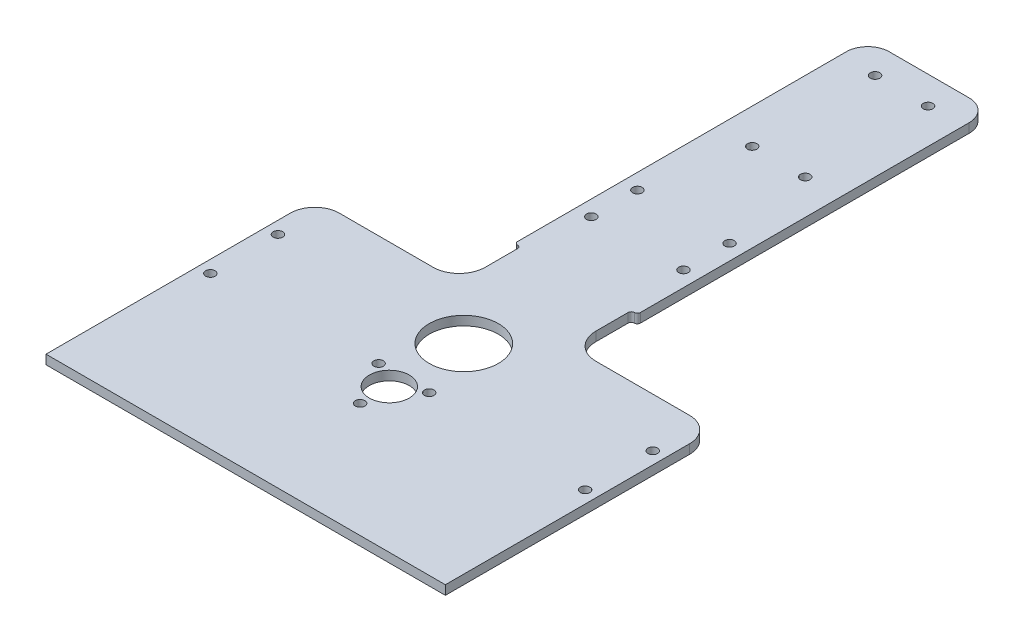
SolidWorks part; units mm, degrees
ref_plane "前视基准面" through (0, 0, 0) normal (0, 0, 1) x (1, 0, 0)
ref_plane "上视基准面" through (0, 0, 0) normal (0, 1, 0) x (1, 0, 0)
ref_plane "右视基准面" through (0, 0, 0) normal (1, 0, 0) x (0, 0, -1)
sketch "草图1" plane through (0, 0, 0) normal (0, 1, 0) x (1, 0, 0)
  line L1 (-100, 100) -> (100, 100)
  line L2 (-100, 100) -> (-100, -100)
  line L3 (-100, -100) -> (100, -100)
  line L4 (100, 100) -> (100, -100)
  line L5 (-100, 100) -> (100, -100) construction
  line L6 (-100, -100) -> (100, 100) construction
  point P0 (0, 0)
  dimension "D1" = 200
  dimension "D2" = 200
extrude "凸台-拉伸1" add sketch "草图1" along normal blind 3
sketch "草图2" plane through (0, 3, 0) normal (0, 1, 0) x (1, 0, 0)
  line L0 (0, 0) -> (0, 91) construction
  line L1 (-100, -100) -> (100, -100) construction
  line L2 (100, 100) -> (-100, 100) construction
  line L3 (-100, 0) -> (100, 0) construction
  line L5 (-100, 100) -> (-100, -100) construction
  line L6 (100, -100) -> (100, 100) construction
  line L7 (-29.5, 0) -> (29.5, 0) construction
  line L8 (-10, 100) -> (10, 100) construction
  line L9 (-10, 100) -> (-10, -100) construction
  line L10 (10, 100) -> (10, -100) construction
  line L11 (0, 0) -> (0, -29) construction
  line L13 (0, -29) -> (0, -32) construction
  circle A0 centre (-29.5, 0) radius 22.5 construction
  circle A1 centre (29.5, 0) radius 22.5 construction
  circle A2 centre (0, -29) radius 10.05 construction
  circle A3 centre (29.5, 0) radius 9.5 construction
  circle A4 centre (29.5, 0) radius 8 construction
  circle A5 centre (-29.5, 0) radius 8 construction
  circle A6 centre (-29.5, 0) radius 9.5 construction
  circle A7 centre (29.5, 9.5) radius 1.5
  circle A8 centre (21.5, 0) radius 1.5
  circle A9 centre (29.5, -9.5) radius 1.5
  circle A10 centre (37.5, 0) radius 1.5
  circle A11 centre (-29.5, -9.5) radius 1.5
  circle A12 centre (-37.5, 0) radius 1.5
  circle A13 centre (-21.5, 0) radius 1.5
  circle A14 centre (-29.5, 9.5) radius 1.5
  point P16 (0, 0)
  dimension "D1" = 45
  dimension "D3" = 20.1
  dimension "D4" = 19
  dimension "D5" = 16
  dimension "D6" = 3
  dimension "D7" = 3
  dimension "D2" = 20
  dimension "D9" = 3
  dimension "D10" = 29
extrude "切除-拉伸2" cut sketch "草图2" against normal blind 10
sketch "草图4" plane through (0, 3, 0) normal (0, 1, 0) x (1, 0, 0)
  line L0 (0, 0) -> (0, 91) construction
  line L1 (100, 100) -> (-100, 100) construction
  line L2 (-10, 100) -> (10, 100)
  line L3 (-10, 100) -> (-10, -100) construction
  line L4 (-100, -100) -> (100, -100) construction
  line L5 (10, 100) -> (10, -100) construction
  line L6 (21.5, 0) -> (37.5, 0)
  line L7 (-29.5, 0) -> (0, 0) construction
  line L8 (0, -29) -> (0, 0) construction
  circle A0 centre (0, -29) radius 11.25
  circle A1 centre (29.5, 0) radius 8 construction
  circle A2 centre (29.5, 0) radius 9.5 construction
  circle A3 centre (29.5, 0) radius 22.5 construction
  circle A4 centre (-29.5, 0) radius 9.5 construction
  circle A5 centre (-29.5, 0) radius 8 construction
  circle A6 centre (-29.5, 0) radius 22.5 construction
  dimension "D1" = 22.5
  dimension "D2" = 19
  dimension "D3" = 16
  dimension "D4" = 45
sketch "草图5" plane through (0, 3, 0) normal (0, 1, 0) x (1, 0, 0)
  line L0 (-44.5, -100) -> (-100, -100)
  line L2 (44.5, 0) -> (44.5, -100)
  line L4 (-20, 47.5) -> (-20, 24.995)
  line L6 (-44.5, 0) -> (-44.5, -100)
  line L7 (-100, -100) -> (100, -100) construction
  line L8 (20, 47.5) -> (20, 24.995)
  line L9 (-100, -100) -> (-100, 100)
  line L10 (0, 0) -> (0, 91) construction
  line L11 (0, 47.5) -> (-20, 47.5)
  line L12 (44.5, -100) -> (-44.5, -100)
  line L13 (0, 47.5) -> (20, 47.5)
  line L14 (-100, 100) -> (100, 100)
  line L15 (100, 100) -> (100, -100)
  line L16 (100, -100) -> (44.5, -100)
  arc A0 (29.8, 14.997) -> (44.5, 0) centre (29.5, 0) cw
  arc A1 (20, 24.995) -> (29.8, 14.997) centre (30, 24.995) ccw
  arc A2 (-29.8, 14.997) -> (-44.5, 0) centre (-29.5, 0) ccw
  arc A3 (-20, 24.995) -> (-29.8, 14.997) centre (-30, 24.995) cw
  line M11 (100, -100) -> (100, 100)
  line M12 (100, 100) -> (-100, 100)
  line M13 (-100, 100) -> (-100, -100)
  line M14 (-100, -100) -> (100, -100)
  dimension "D1" = 10
  dimension "D2" = 15
extrude "切除-拉伸3" cut sketch "草图5" against normal blind 10 contours A3 L4 L11 L13 L8 A1 A0 L2 L6 A2 M14 M11 M12 M13 region at (-72.25, 3, 97.1716)
sketch "草图6" plane through (0, 0, 0) normal (0, -1, 0) x (1, 0, 0)
  line L0 (20, -47.5) -> (-20, -47.5) construction
  line L7 (-20, -47.5) -> (-20, -24.995) construction
  circle A1 centre (-15, -42.5) radius 1.55
  circle A2 centre (-15, -27.5) radius 1.55
  circle A3 centre (15, -27.5) radius 1.55
  circle A4 centre (15, -42.5) radius 1.55
  dimension "D1" = 3.1
  dimension "D2" = 5
  dimension "D3" = 5
  dimension "D4" = 30
extrude "φ3.1通孔1" cut sketch "草图6" against normal blind 10
sketch "草图9" plane through (0, 3, 0) normal (0, 1, 0) x (1, 0, 0)
  line L0 (-20, 47.5) -> (-20, 26.3383)
  line L4 (-20, 47.5) -> (20, 47.5)
  line L5 (20, 47.5) -> (20, 26.3383)
  line L8 (12.2609, 20.995) -> (-12.2609, 20.995)
  arc A0 (-18.8003, 24.5054) -> (-13.4605, 21.3948) centre (-29.5, 0) cw
  arc A1 (18.8003, 24.5054) -> (13.4605, 21.3948) centre (29.5, 0) ccw
  arc A2 (18.8003, 24.5054) -> (20, 26.3383) centre (18, 26.3383) ccw
  arc A3 (13.4605, 21.3948) -> (12.2609, 20.995) centre (12.2609, 22.995) cw
  arc A4 (-12.2609, 20.995) -> (-13.4605, 21.3948) centre (-12.2609, 22.995) cw
  arc A5 (-18.8003, 24.5054) -> (-20, 26.3383) centre (-18, 26.3383) cw
  point P20 (-20, 24.995)
  dimension "D1" = 2
sketch "草图11" plane through (0, 3, 0) normal (0, 1, 0) x (1, 0, 0)
  line L0 (44.5, -17.5) -> (44.5, -100)
  line L1 (20, 47.5) -> (20, 7.5)
  line L2 (-44.5, 0) -> (-44.5, -100) construction
  line L3 (-44.5, -17.5) -> (-44.5, -100)
  line L4 (0, 47.5) -> (0, -100) construction
  line L5 (20, 47.5) -> (-20, 47.5) construction
  line L6 (-44.5, -100) -> (44.5, -100) construction
  line L7 (18, -4) -> (18, 6.5)
  line L8 (20, 7.5) -> (19, 7.5)
  line L9 (-39.5, -12.5) -> (-44.5, -12.5)
  line L10 (26.5, -12.5) -> (39.5, -12.5)
  line L11 (20, 47.5) -> (101.1331, 47.5)
  line L12 (101.1331, 47.5) -> (101.1331, -100)
  line L13 (101.1331, -100) -> (44.5, -100)
  line L14 (-20, 47.5) -> (-20, 7.5)
  line L15 (-20, 7.5) -> (-19, 7.5)
  line L16 (-18, -4) -> (-18, 6.5)
  line L17 (-26.5, -12.5) -> (-39.5, -12.5)
  line L18 (-44.5, -12.5) -> (-44.5, -17.5)
  line L19 (-101.1331, -100) -> (-44.5, -100)
  line L20 (-101.1331, 47.5) -> (-101.1331, -100)
  line L21 (-20, 47.5) -> (-101.1331, 47.5)
  line L22 (39.5, -12.5) -> (44.5, -12.5)
  line L23 (44.5, 0) -> (44.5, -100) construction
  line L24 (44.5, -12.5) -> (44.5, -17.5)
  arc A0 (26.5, -12.5) -> (18, -4) centre (26.5, -4) cw
  circle A2 centre (29.5, -9.5) radius 1.5
  circle A4 centre (21.5, 0) radius 1.5
  arc A5 (18, 6.5) -> (19, 7.5) centre (19, 6.5) cw
  arc A6 (-18, 6.5) -> (-19, 7.5) centre (-19, 6.5) ccw
  arc A7 (-26.5, -12.5) -> (-18, -4) centre (-26.5, -4) ccw
  point P21 (-44.5, -12.5)
  dimension "D1" = 8.5
  dimension "D2" = 1
extrude "切除-拉伸6" cut sketch "草图11" against normal up to next
extrude "φ22.5落弹孔" cut sketch "草图4" against normal up to next contours A0 region at (0, 3, 29)
fillet "圆角1" radius 1 2 edges at (-20, 1.5, -7.5) (20, 1.5, -7.5)
sketch "草图12" plane through (0, 0, -47.5) normal (0, 0, -1) x (-1, 0, 0)
  line L0 (-20, 3) -> (-20, 0)
  line L1 (-20, 0) -> (20, 0)
  line L2 (20, 0) -> (20, 3)
  line L3 (20, 3) -> (-20, 3)
extrude "凸台-拉伸2" add sketch "草图12" along normal blind 75
fillet "圆角2" radius 7 2 edges at (-20, 1.5, -122.5) (20, 1.5, -122.5)
sketch "草图13" plane through (0, 3, 0) normal (0, 1, 0) x (1, 0, 0)
  line L0 (-20, 115.5) -> (-20, 8.5) construction
  line L1 (0, 122.5) -> (0, 107.278)
  line L2 (-13, 122.5) -> (13, 122.5) construction
  circle A0 centre (-8.625, 73.5) radius 1.55
  circle A1 centre (-15, 42.5) radius 1.55
  circle A2 centre (-8.625, 113.5) radius 1.55
  circle A3 centre (8.625, 73.5) radius 1.55
  circle A4 centre (8.625, 113.5) radius 1.55
  dimension "D3" = 3.1
  dimension "D5" = 3.1
  dimension "D1" = 31
  dimension "D2" = 11.375
  dimension "D4" = 40
extrude "φ3.1通孔" cut sketch "草图13" against normal blind 10 contours A2 | A4 | A3 | A0 region at (-8.625, 3, -73.5) region at (-8.625, 3, -113.5) region at (8.625, 3, -73.5) region at (8.625, 3, -113.5)
sketch "草图16" plane through (0, 3, 0) normal (0, 1, 0) x (1, 0, 0)
  circle A0 centre (0, -53.25) radius 13 construction
  circle A2 centre (0, -53.25) radius 33 construction
  circle A3 centre (0, -53.25) radius 35.5 construction
  circle A4 centre (0, -53.25) radius 9.5 construction
  circle A5 centre (0, -62.75) radius 1.55
  circle A6 centre (-8.2272, -48.5) radius 1.55
  circle A7 centre (8.2272, -48.5) radius 1.55
  circle A8 centre (0, -53.25) radius 6.5
  point P16 (0, -53.25)
  dimension "D1" = 26
  dimension "D2" = 66
  dimension "D3" = 71
  dimension "D4" = 19
  dimension "D5" = 3.1
  dimension "D7" = 13
  dimension "D6" = 3
extrude "拨弹电机固定" cut sketch "草图16" against normal blind 10
sketch "草图18" plane through (-44.5, 0, 0) normal (-1, 0, 0) x (0, 0, 1)
  line L0 (12.5, 3) -> (12.5, 0)
  line L1 (12.5, 0) -> (100, 0)
  line L2 (100, 0) -> (100, 3)
  line L3 (100, 3) -> (12.5, 3)
extrude "凸台-拉伸3" add sketch "草图18" along normal blind 20.5
sketch "草图19" plane through (44.5, 0, 0) normal (1, 0, 0) x (0, 0, -1)
  line L0 (-100, 3) -> (-100, 0)
  line L1 (-100, 0) -> (-12.5, 0)
  line L2 (-12.5, 0) -> (-12.5, 3)
  line L3 (-12.5, 3) -> (-100, 3)
extrude "凸台-拉伸4" add sketch "草图19" along normal blind 20.5
sketch "草图7" plane through (0, 3, 0) normal (0, 1, 0) x (1, 0, 0)
  line L0 (0, -29) -> (0, -14.1048)
  line L1 (-25.4783, -39.524) -> (-25.4783, -40.524)
  line L3 (-65, -100) -> (-65, -12.5) construction
  circle A0 centre (-61, -50.5) radius 1.55
  circle A1 centre (-61, -28.5) radius 1.55
  circle A3 centre (61, -50.5) radius 1.55
  circle A4 centre (61, -28.5) radius 1.55
  point P9 (-51, -22.5)
  dimension "D1" = 4
  dimension "D3" = 3.1
  dimension "D4" = 22
  dimension "D2" = 10
extrude "切除-拉伸7" cut sketch "草图7" against normal blind 20.5 contours A1 | A0 | A4 | A3 region at (-61, 3, 50.5) region at (-61, 3, 28.5) region at (61, 3, 50.5) region at (61, 3, 28.5)
fillet "圆角3" radius 8 2 edges at (65, 1.5, 12.5) (-65, 1.5, 12.5)
sketch "草图20" plane through (0, 3, 0) normal (0, 1, 0) x (1, 0, 0)
  circle A0 centre (0, -53.25) radius 33 construction
  circle A1 centre (0, -53.25) radius 34.5 construction
  circle A2 centre (0, -29) radius 11
  dimension "D1" = 69
  dimension "D2" = 66
  dimension "D3" = 22
